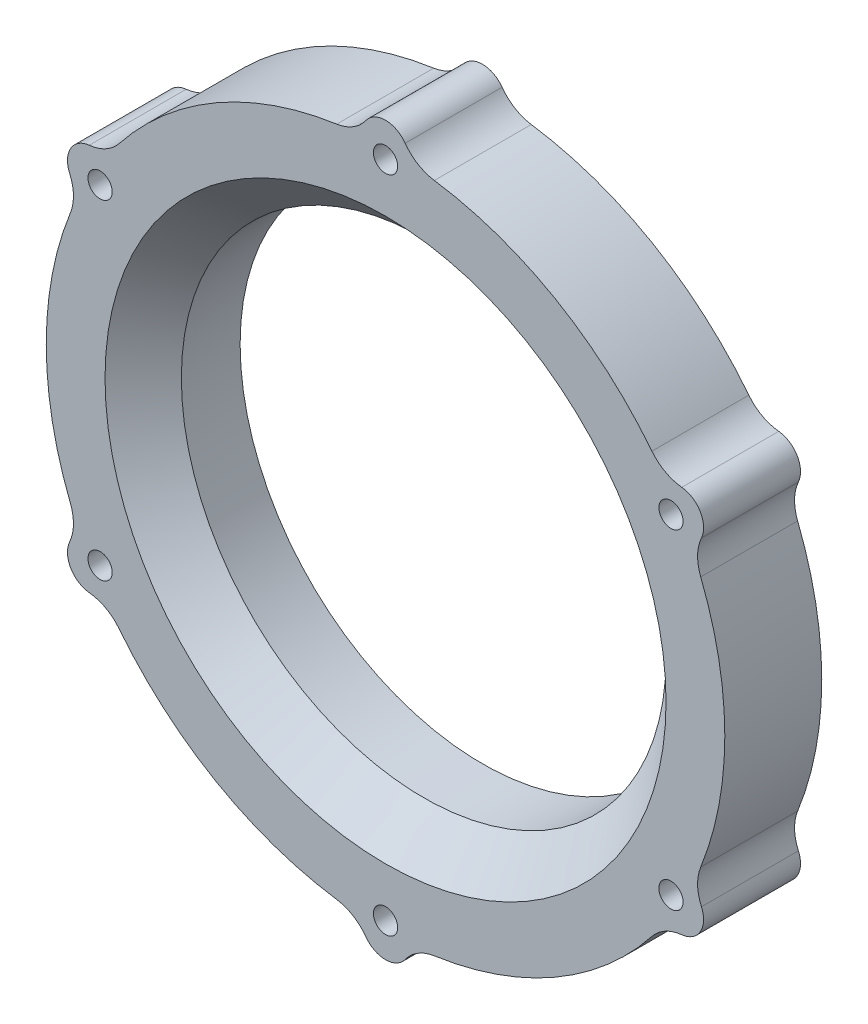
SolidWorks part; units mm, degrees
material "6061-T6 (SS)"
ref_plane "Front Plane" through (0, 0, 0) normal (0, 0, 1) x (1, 0, 0)
ref_plane "Top Plane" through (0, 0, 0) normal (0, 1, 0) x (1, 0, 0)
ref_plane "Right Plane" through (0, 0, 0) normal (1, 0, 0) x (0, 0, -1)
sketch "Sketch1" plane through (0, 0, 0) normal (0, 0, 1) x (1, 0, 0)
  line L0 (0, 0) -> (88.9, 0) construction
  line L1 (0, 0) -> (76.9897, 44.45) construction
  line L2 (0, 0) -> (76.9897, -44.45) construction
  line L3 (0, 0) -> (0, -88.9) construction
  line L4 (0, 0) -> (-76.9897, -44.45) construction
  line L5 (0, 0) -> (-76.9897, 44.45) construction
  line L6 (0, 0) -> (0, 88.9) construction
  circle A0 centre (0, 0) radius 88.9
  circle A1 centre (0, 0) radius 63.5
  circle A2 centre (76.9897, 44.45) radius 6.35
  circle A3 centre (76.9897, -44.45) radius 6.35
  circle A4 centre (0, -88.9) radius 6.35
  circle A5 centre (-76.9897, -44.45) radius 6.35
  circle A6 centre (-76.9897, 44.45) radius 6.35
  circle A7 centre (0, 88.9) radius 6.35
  point P14 (0, 0)
  point P20 (0, 0)
  dimension "D1" = 177.8
  dimension "D2" = 127
  dimension "D5" = 12.7
  dimension "D3" = 30
  dimension "D4" = 6
extrude "Boss-Extrude1" add sketch "Sketch1" along normal blind 25.4 contours A7 A0 A6 A5 A4 A3 A2 A1 | A0 A7 | A0 A7 | A0 A2 | A0 A2 | A0 A3 | A0 A3 | A0 A4 | A0 A4 | A0 A5 | A0 A5 | A0 A6 | A0 A6 region at (84.1904, -19.3646, 0) region at (74.6207, 43.0823, 0) region at (79.2879, 45.7769, 0) region at (79.2879, -45.7769, 0) region at (74.6207, -43.0823, 0) region at (0, 86.1645, 0) region at (0, 91.5538, 0) region at (0, -91.5538, 0) region at (0, -86.1645, 0) region at (-74.6207, 43.0823, 0) region at (-79.2879, 45.7769, 0) region at (-79.2879, -45.7769, 0) region at (-74.6207, -43.0823, 0)
chamfer "Chamfer1" distance 10 angle 45 1 edges at (63.5, 0, 25.4)
sketch "Sketch3" plane through (0, 0, 25.4) normal (0, 0, 1) x (1, 0, 0)
  line L0 (0, 0) -> (74.79, 43.18) construction
  line L1 (0, 0) -> (86.36, 0) construction
  circle A7 centre (0, 0) radius 86.36
  circle A8 centre (74.79, 43.18) radius 3.175
  circle A9 centre (74.79, -43.18) radius 3.175
  circle A10 centre (0, -86.36) radius 3.175
  circle A11 centre (-74.79, -43.18) radius 3.175
  circle A12 centre (-74.79, 43.18) radius 3.175
  circle A13 centre (0, 86.36) radius 3.175
  point P15 (0, 0)
  point P20 (0, 0)
  dimension "D1" = 172.72
  dimension "D3" = 6.35
  dimension "D2" = 30
  dimension "D4" = 6
extrude "Cut-Extrude1" cut sketch "Sketch3" against normal through all contours A7 A8 | A7 A8 | A7 A13 | A7 A13 | A7 A12 | A7 A12 | A7 A10 | A7 A10 | A7 A9 | A7 A9 | A11 region at (73.6139, 42.501, 25.4) region at (75.9478, 43.8485, 25.4) region at (75.9478, -43.8485, 25.4) region at (73.6139, -42.501, 25.4) region at (0, 85.002, 25.4) region at (0, 87.6969, 25.4) region at (0, -87.6969, 25.4) region at (0, -85.002, 25.4) region at (-73.6139, 42.501, 25.4) region at (-75.9478, 43.8485, 25.4)
fillet "Fillet1" radius 11.43 12 edges at (73.6203, 49.8324, 12.7) (79.9662, 38.8409, 12.7) (79.9662, -38.8409, 12.7) (73.6203, -49.8324, 12.7) (6.3459, -88.6732, 12.7) (-6.3459, -88.6732, 12.7) (-73.6203, -49.8324, 12.7) (-79.9662, -38.8409, 12.7) (-79.9662, 38.8409, 12.7) (-73.6203, 49.8324, 12.7) (-6.3459, 88.6732, 12.7) (6.3459, 88.6732, 12.7)
